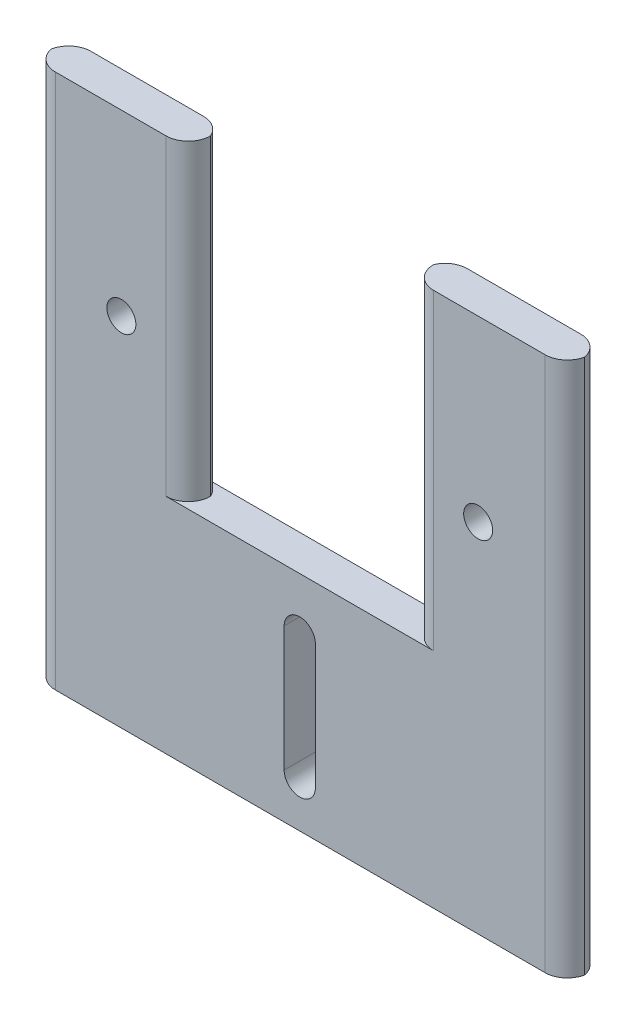
SolidWorks part; units mm, degrees
ref_plane "Front Plane" through (0, 0, 0) normal (0, 0, 1) x (1, 0, 0)
ref_plane "Top Plane" through (0, 0, 0) normal (0, 1, 0) x (1, 0, 0)
ref_plane "Right Plane" through (0, 0, 0) normal (1, 0, 0) x (0, 0, -1)
sketch "Sketch1" plane through (0, 0, 0) normal (0, 0, 1) x (1, 0, 0)
  line L1 (70, -60) -> (-70, -60)
  line L2 (70, -60) -> (70, 60)
  line L3 (70, 60) -> (-70, 60)
  line L4 (-70, -60) -> (-70, 60)
  line L5 (70, -60) -> (-70, 60) construction
  line L6 (70, 60) -> (-70, -60) construction
  point P0 (0, 0)
extrude "Boss-Extrude1" add sketch "Sketch1" along normal blind 8
sketch "Sketch2" plane through (0, 0, 8) normal (0, 0, 1) x (1, 0, 0)
  circle A0 centre (-40, 20) radius 3.25
  circle A1 centre (40, 20) radius 3.25
  dimension "D3" = 6.5
  dimension "D6" = 6.5
  dimension "D1" = 30
  dimension "D2" = 80
  dimension "D4" = 30
  dimension "D5" = 40
extrude "Cut-Extrude1" cut sketch "Sketch2" against normal through all
sketch "Sketch3" plane through (0, 0, 8) normal (0, 0, 1) x (1, 0, 0)
  line L0 (0, -49.9) -> (0, -21.9) construction
  line L1 (-3.5, -49.9) -> (-3.5, -21.9)
  line L2 (3.5, -49.9) -> (3.5, -21.9)
  arc A0 (-3.5, -49.9) -> (3.5, -49.9) centre (0, -49.9) ccw
  arc A1 (3.5, -21.9) -> (-3.5, -21.9) centre (0, -21.9) ccw
  point P3 (0, -35.9)
  point P8 (0, -53.4)
  dimension "D1" = 6.6
extrude "Cut-Extrude2" cut sketch "Sketch3" against normal through all contours L2 A1 L1 A0
sketch "Sketch5" plane through (0, 0, 8) normal (0, 0, 1) x (1, 0, 0)
  line L1 (25, -10) -> (-25, -10)
  line L2 (25, -10) -> (25, 60)
  line L3 (25, 60) -> (-25, 60)
  line L4 (-25, -10) -> (-25, 60)
  line L5 (25, -10) -> (-25, 60) construction
  line L6 (25, 60) -> (-25, -10) construction
  point P0 (0, 25)
  dimension "D1" = 45
  dimension "D2" = 45
  dimension "D5" = 50
extrude "Cut-Extrude3" cut sketch "Sketch5" against normal through all
fillet "Fillet2" radius 5 2 edges at (25, 25, 8) (-25, 25, 8)
fillet "Fillet3" radius 5 2 edges at (25, 25, 0) (-25, 25, 0)
sketch "Sketch6" plane through (0, 0, 8) normal (0, 0, 1) x (1, 0, 0)
  line L1 (-70, -60) -> (-59.8207, -60)
  line L2 (-70, -60) -> (-70, 60.0093)
  line L3 (-70, 60.0093) -> (-59.8207, 60.0093)
  line L4 (-59.8207, -60) -> (-59.8207, 60.0093)
  line L5 (70, -60) -> (60, -60)
  line L6 (70, -60) -> (70, 60)
  line L7 (70, 60) -> (60, 60)
  line L8 (60, -60) -> (60, 60)
  dimension "D1" = 0
  dimension "D2" = 0
  dimension "D3" = 0
extrude "Cut-Extrude4" cut sketch "Sketch6" against normal through all
fillet "Fillet4" radius 5 4 edges at (60, 0, 0) (60, 0, 8) (-59.8207, 0, 0) (-59.8207, 0, 8)
